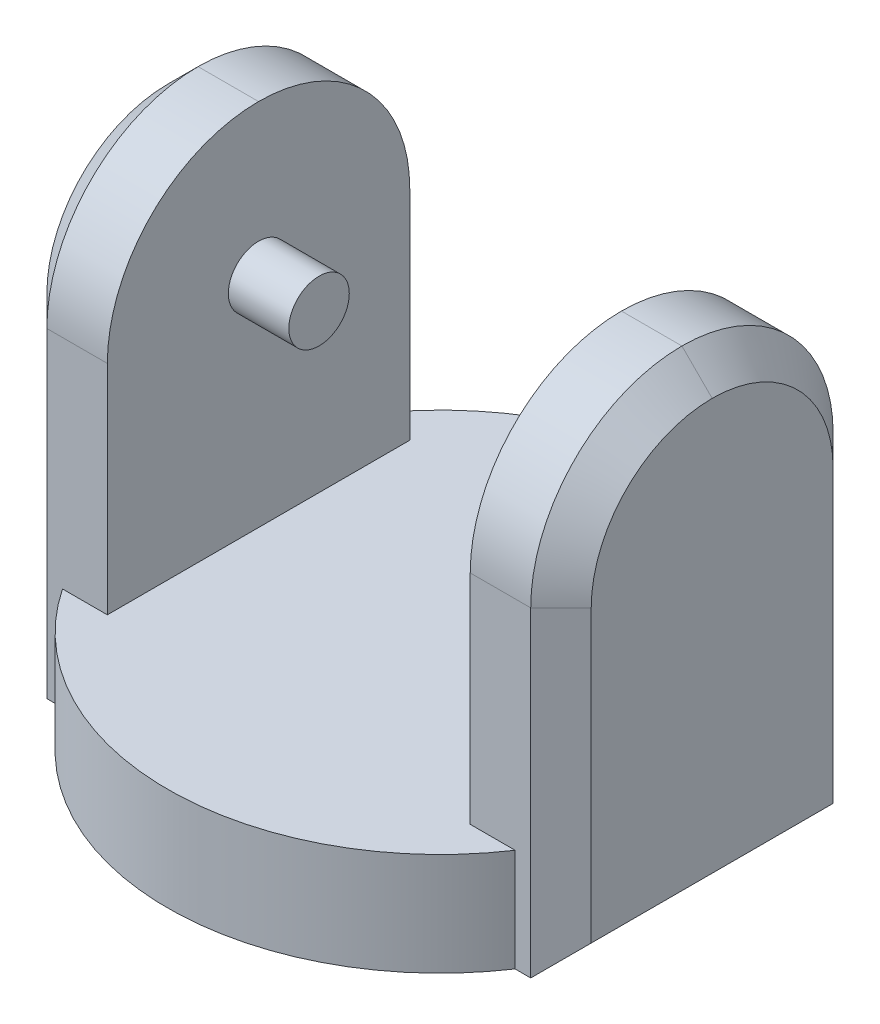
SolidWorks part; units mm, degrees
ref_plane "Front Plane" through (0, 0, 0) normal (0, 0, 1) x (1, 0, 0)
ref_plane "Top Plane" through (0, 0, 0) normal (0, 1, 0) x (1, 0, 0)
ref_plane "Right Plane" through (0, 0, 0) normal (1, 0, 0) x (0, 0, -1)
sketch "Sketch1" plane through (0, 0, 0) normal (0, 1, 0) x (1, 0, 0)
  circle A0 centre (0, 0) radius 45
  dimension "D1" = 90
extrude "Boss-Extrude1" add sketch "Sketch1" along normal blind 17
ref_plane "Plane1" through (45, 0, 0) normal (1, 0, 0) x (0, 0, -1)
ref_plane "Plane2" through (-45, 0, 0) normal (1, 0, 0) x (0, 0, -1)
sketch "Sketch2" plane through (45, 0, 0) normal (1, 0, 0) x (0, 0, -1)
  line L1 (-25, 0) -> (25, 0)
  line L2 (-25, 0) -> (-25, 78)
  line L3 (-25, 78) -> (25, 78)
  line L4 (25, 0) -> (25, 78)
  point P4 (0, 0)
  dimension "D1" = 78
  dimension "D2" = 50
extrude "Boss-Extrude2" add sketch "Sketch2" against normal blind 15
sketch "Sketch3" plane through (-45, 0, 0) normal (1, 0, 0) x (0, 0, -1)
  line L1 (-25, 0) -> (25, 0)
  line L2 (-25, 0) -> (-25, 78)
  line L3 (-25, 78) -> (25, 78)
  line L4 (25, 0) -> (25, 78)
extrude "Boss-Extrude3" add sketch "Sketch3" along normal blind 15
fillet "Fillet1" radius 25 4 edges at (37.5, 78, -25) (37.5, 78, 25) (-37.5, 78, 25) (-37.5, 78, -25)
chamfer "Chamfer1" distance 5 angle 45 10 edges at (-45, 0, 0) (-45, 26.5, -25) (-45, 26.5, 25) (-45, 70.6777, -17.6777) (-45, 70.6777, 17.6777) (45, 26.5, -25) (45, 70.6777, -17.6777) (45, 70.6777, 17.6777) (45, 0, 0) (45, 26.5, 25)
sketch "Sketch4" plane through (-30, 0, 0) normal (1, 0, 0) x (0, 0, -1)
  circle A0 centre (0, 53) radius 5
  dimension "D1" = 10
  dimension "D2" = 25
extrude "Boss-Extrude4" add sketch "Sketch4" along normal blind 10
sketch "Sketch5" plane through (0, 0, 0) normal (0, -1, 0) x (-1, 0, 0)
  circle A0 centre (0, 0) radius 5
  dimension "D1" = 10
extrude "Cut-Extrude1" cut sketch "Sketch5" against normal blind 10
